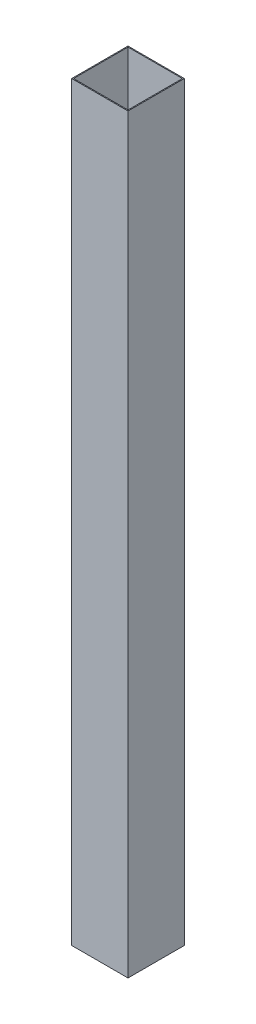
SolidWorks part; units mm, degrees
ref_plane "Front" through (0, 0, 0) normal (0, 0, 1) x (1, 0, 0)
ref_plane "Top" through (0, 0, 0) normal (0, 1, 0) x (1, 0, 0)
ref_plane "Right" through (0, 0, 0) normal (1, 0, 0) x (0, 0, -1)
sketch "Sketch1" plane through (0, 0, 0) normal (0, 1, 0) x (1, 0, 0)
  line L0 (-73.66, 73.66) -> (73.66, 73.66)
  line L1 (-76.2, 76.2) -> (76.2, 76.2)
  line L2 (-76.2, 76.2) -> (-76.2, -76.2)
  line L3 (-76.2, -76.2) -> (76.2, -76.2)
  line L4 (76.2, 76.2) -> (76.2, -76.2)
  line L5 (-76.2, 76.2) -> (76.2, -76.2) construction
  line L6 (-76.2, -76.2) -> (76.2, 76.2) construction
  line L7 (73.66, 73.66) -> (73.66, -73.66)
  line L8 (-73.66, -73.66) -> (73.66, -73.66)
  line L9 (-73.66, 73.66) -> (-73.66, -73.66)
  point P0 (0, 0)
  dimension "D1" = 152.4
  dimension "D2" = 152.4
  dimension "D3" = 2.54
extrude "Boss-Extrude1" add sketch "Sketch1" along normal blind 6604
sketch "Sketch2" plane through (0, 0, 76.2) normal (0, 0, 1) x (1, 0, 0)
  line L0 (76.2, 6604) -> (76.2, 0) construction
  line L1 (-76.2, 6604) -> (76.2, 6604)
  line L2 (-76.2, 6604) -> (-76.2, 2032)
  line L3 (-76.2, 2032) -> (76.2, 2032)
  line L4 (76.2, 6604) -> (76.2, 2032)
  dimension "D1" = 2032
extrude "Cut-Extrude1" cut sketch "Sketch2" against normal through all
sketch "Sketch3" [suppressed] plane through (0, 0, 0) normal (0, -1, 0) x (1, 0, 0)
  line L4 (76.2, -76.2) -> (76.2, 76.2)
  line L5 (76.2, 76.2) -> (-76.2, 76.2)
  line L6 (-76.2, 76.2) -> (-76.2, -76.2)
  line L7 (-76.2, -76.2) -> (76.2, -76.2)
  line L8 (76.2, -76.2) -> (76.2, 76.2)
  line L9 (76.2, 76.2) -> (-76.2, 76.2)
  line L10 (-76.2, 76.2) -> (-76.2, -76.2)
  line L11 (-76.2, -76.2) -> (76.2, -76.2)
  dimension "D1" = 0
extrude "Cut-Extrude2" [suppressed] cut sketch "Sketch3" against normal offset from surface (4572 mm away) 508 up to face at (0, 2032, 0)
